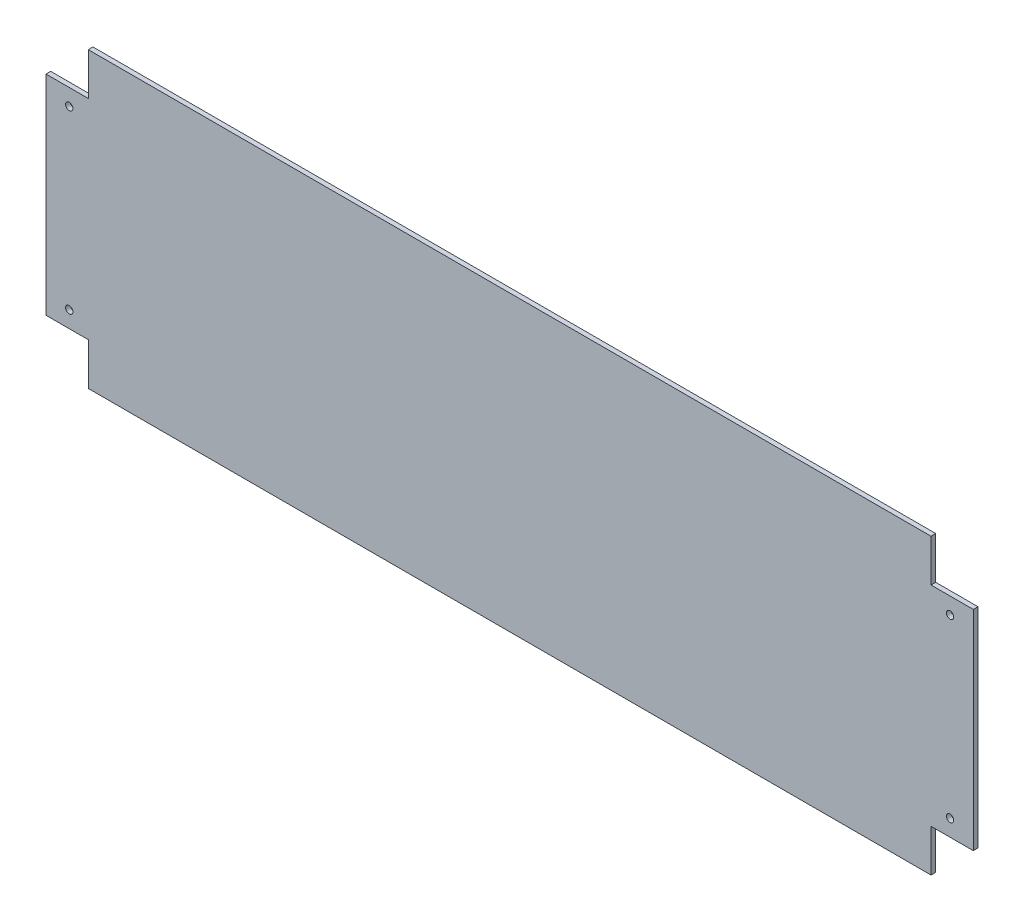
SolidWorks part; units mm, degrees
ref_plane "Plan de face" through (0, 0, 0) normal (0, 0, 1) x (1, 0, 0)
ref_plane "Plan de dessus" through (0, 0, 0) normal (0, 1, 0) x (1, 0, 0)
ref_plane "Plan de droite" through (0, 0, 0) normal (1, 0, 0) x (0, 0, -1)
sketch "Sketch1" plane through (0, 0, 0) normal (0, 0, 1) x (1, 0, 0)
  line L1 (-197.5, 62.5) -> (197.5, 62.5)
  line L2 (-197.5, 62.5) -> (-197.5, -62.5)
  line L3 (-197.5, -62.5) -> (197.5, -62.5)
  line L4 (197.5, 62.5) -> (197.5, -62.5)
  line L5 (-197.5, 62.5) -> (197.5, -62.5) construction
  line L6 (-197.5, -62.5) -> (197.5, 62.5) construction
  point P0 (0, 0)
  dimension "D1" = 125
  dimension "D2" = 395
extrude "Boss-Extrude1" add sketch "Sketch1" along normal blind 2
sketch "Sketch2" plane through (0, 0, 2) normal (0, 0, 1) x (1, 0, 0)
  line L1 (-187.6, 37.5) -> (187.6, 37.5) construction
  line L2 (-187.6, 37.5) -> (-187.6, -37.5) construction
  line L3 (-187.6, -37.5) -> (187.6, -37.5) construction
  line L4 (187.6, 37.5) -> (187.6, -37.5) construction
  line L5 (-187.6, 37.5) -> (187.6, -37.5) construction
  line L6 (-187.6, -37.5) -> (187.6, 37.5) construction
  circle A0 centre (-187.6, 37.5) radius 1.55
  circle A1 centre (-187.6, -37.5) radius 1.55
  circle A2 centre (187.6, 37.5) radius 1.55
  circle A3 centre (187.6, -37.5) radius 1.55
  point P0 (0, 0)
  dimension "D1" = 75
  dimension "D2" = 375.2
extrude "Cut-Extrude1" cut sketch "Sketch2" against normal through all
sketch "Sketch3" plane through (0, 0, 2) normal (0, 0, 1) x (1, 0, 0)
  line L1 (-197.5, 62.5) -> (-179.5, 62.5)
  line L2 (-197.5, 62.5) -> (-197.5, 44.5)
  line L3 (-197.5, 44.5) -> (-179.5, 44.5)
  line L4 (-179.5, 62.5) -> (-179.5, 44.5)
  dimension "D1" = 18
extrude "Cut-Extrude2" cut sketch "Sketch3" against normal through all
mirror "Mirror1" about plane through (0, 0, 0) normal (0, 1, 0) of "Cut-Extrude2"
mirror "Mirror2" about plane through (0, 0, 0) normal (1, 0, 0) of "Mirror1"
